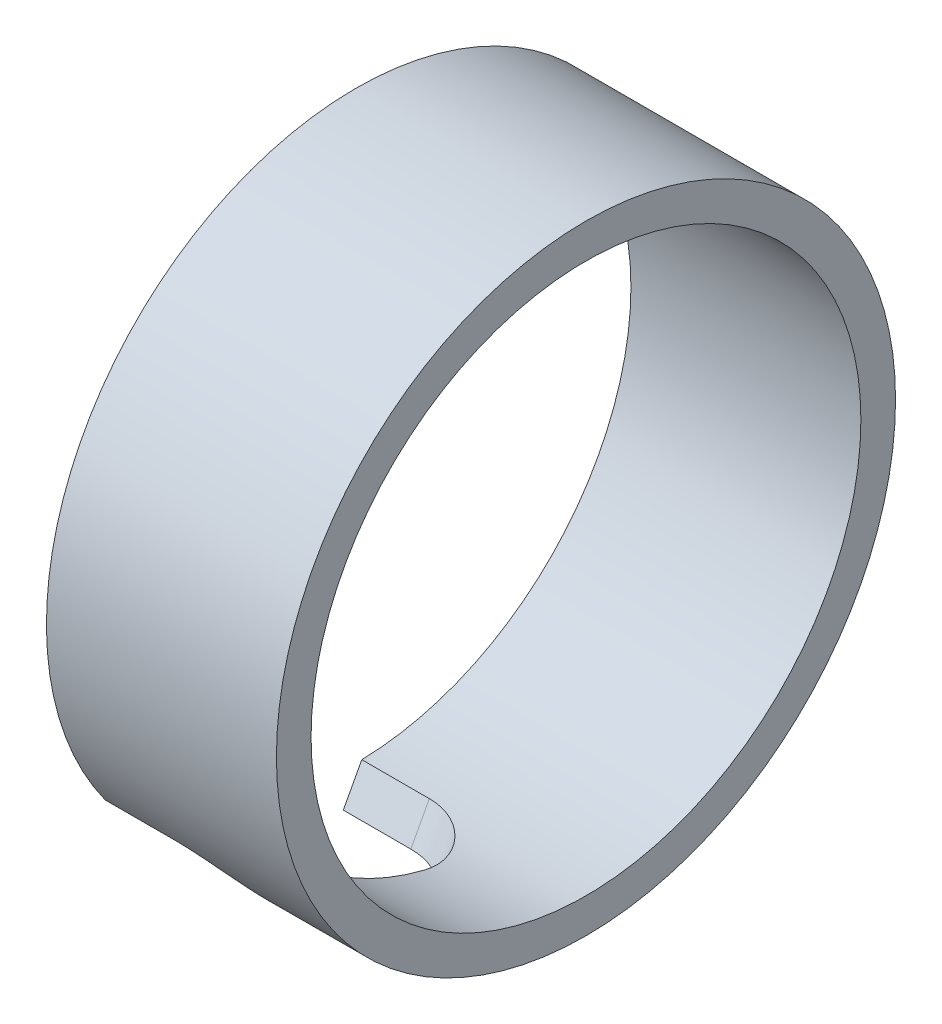
SolidWorks part; units mm, degrees
material "Nylon 6/10"
ref_plane "Front Plane" through (0, 0, 0) normal (0, 0, 1) x (1, 0, 0)
ref_plane "Top Plane" through (0, 0, 0) normal (0, 1, 0) x (1, 0, 0)
ref_plane "Right Plane" through (0, 0, 0) normal (1, 0, 0) x (0, 0, -1)
sketch "Sketch1" plane through (0, 0, 0) normal (0, 0, 1) x (1, 0, 0)
  line L0 (-31.75, 7.5) -> (-48.665, 7.5) construction
  line L1 (-39.013, 8.7312) -> (-32.527, 8.7312)
  line L2 (-39.013, 8.7312) -> (-39.013, 7.754)
  line L3 (-39.013, 7.754) -> (-32.527, 7.754)
  line L4 (-32.527, 8.7312) -> (-32.527, 7.754)
  line L5 (-39.14, 0.8917) -> (-39.14, 6.8403) construction
  line L6 (-32.4, 15.2446) -> (-32.4, -15.2446) construction
  line L7 (0, 0) -> (-47.1489, 0) construction
  dimension "D1" = 0.254
  dimension "D2" = 0.127
  dimension "D3" = 0.127
  dimension "D4" = 17.4625
revolve "Revolve1" add sketch "Sketch1" angle 360 about L7
ref_plane "Plane1" through (0, 0, 0) normal (0, -0.8811, 0.4729) x (1, 0, 0)
sketch "Sketch3" plane through (0, 0, 0) normal (0, -0.8811, 0.4729) x (1, 0, 0)
  line L0 (-39.013, 3.81) -> (-39.013, -3.81)
  line L1 (-39.013, 7.754) -> (-39.013, -7.754) construction
  line L2 (-39.013, -3.81) -> (-37.108, -3.81)
  line L3 (-35.203, -1.905) -> (-35.203, 1.905)
  line L4 (-37.108, 3.81) -> (-39.013, 3.81)
  line L5 (-39.013, 8.7313) -> (-39.013, -8.7312) construction
  line L6 (-39.013, 8.7313) -> (-39.013, -8.7312) construction
  line L7 (-35.203, 0) -> (-39.013, 0) construction
  arc A0 (-37.108, -3.81) -> (-35.203, -1.905) centre (-37.108, -1.905) ccw
  arc A1 (-35.203, 1.905) -> (-37.108, 3.81) centre (-37.108, 1.905) ccw
  dimension "D1" = 7.62
  dimension "D2" = 3.81
extrude "Cut-Extrude1" cut sketch "Sketch3" along normal up to next
